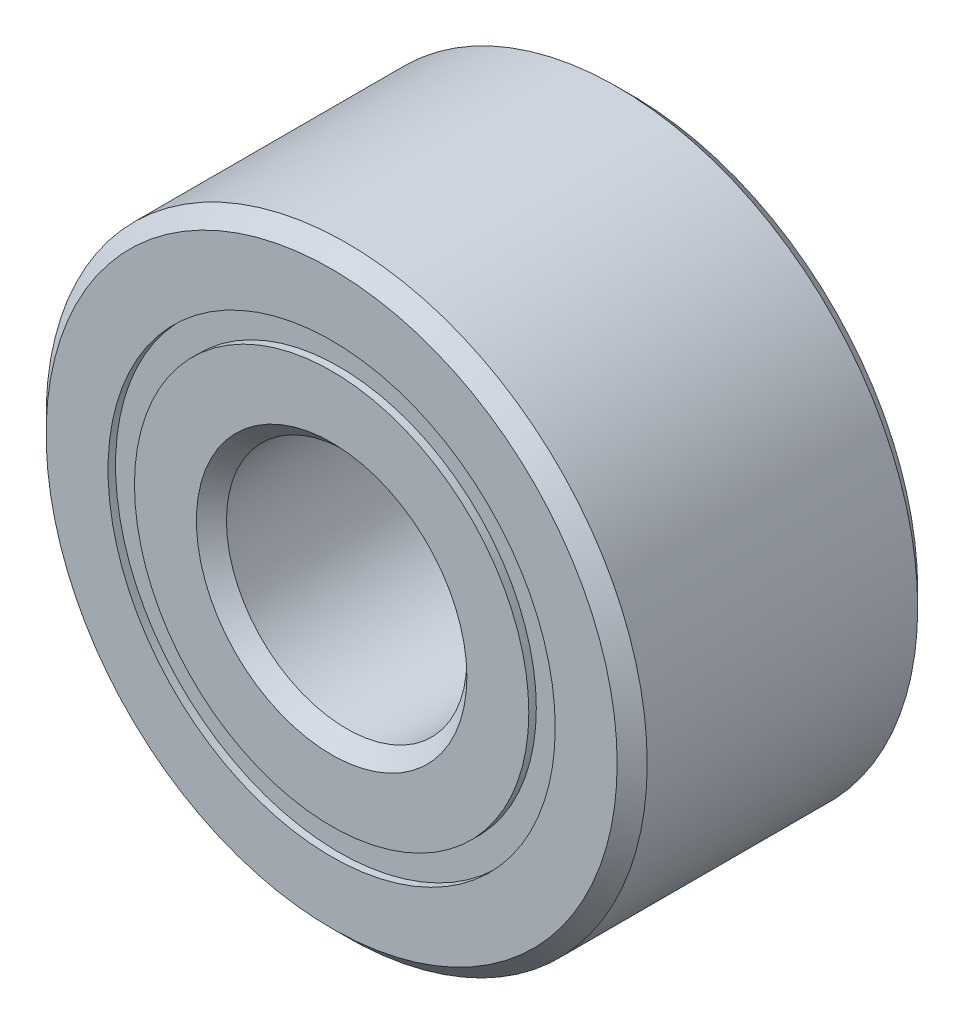
SolidWorks part; units mm, degrees
material "Stainless Steel (ferritic)"
ref_plane "Front Plane" through (0, 0, 0) normal (0, 0, 1) x (1, 0, 0)
ref_plane "Top Plane" through (0, 0, 0) normal (0, 1, 0) x (1, 0, 0)
ref_plane "Right Plane" through (0, 0, 0) normal (1, 0, 0) x (0, 0, -1)
sketch "Sketch1" plane through (0, 0, 0) normal (1, 0, 0) x (0, 0, -1)
  line L0 (-1.25, 0) -> (1.25, 0) construction
  line L1 (0, 2.5) -> (0, -2.5) construction
  line L2 (1.125, 2.5) -> (-1.125, 2.5)
  line L3 (-1.125, 2.5) -> (-1.25, 2.375)
  line L4 (-1.25, 2.375) -> (-1.25, 1.8599)
  line L5 (-1.25, 1.8599) -> (-0.5556, 1.8599)
  line L6 (1.25, 1.8599) -> (0.5556, 1.8599)
  line L7 (1.25, 2.375) -> (1.25, 1.8599)
  line L8 (1.125, 2.5) -> (1.25, 2.375)
  line L9 (0, 2.5) -> (0, 1.75) construction
  line L10 (0, 1.75) -> (0, 1) construction
  arc A0 (-0.5556, 1.8599) -> (0.5556, 1.8599) centre (0, 1.75) cw
  point P14 (0, 1)
  dimension "Width" = 2.5
  dimension "OD" = 5
  dimension "D1" = 45
  dimension "D2" = 0.125
  dimension "Shaft Dia" = 2
  dimension "D3" = 1.1111
  dimension "D4" = 0.1099
revolve "Revolve1" add sketch "Sketch1" angle 360 about L0
sketch "Sketch3" plane through (0, 0, 0) normal (1, 0, 0) x (0, 0, -1)
  line L0 (-1.25, 1.6401) -> (-0.5556, 1.6401)
  line L1 (0, 2.5) -> (0, -2.5) construction
  line L2 (-1.25, 2.375) -> (-1.25, 1.8599) construction
  line L3 (-1.25, 1.6401) -> (-1.25, 1.125)
  line L4 (-1.125, 2.5) -> (-1.25, 2.375) construction
  line L5 (-1.25, 1.125) -> (-1.125, 1)
  line L6 (-1.125, 1) -> (1.125, 1)
  line L7 (1.125, 2.5) -> (1.125, -2.5) construction
  line L8 (1.125, 1) -> (1.25, 1.125)
  line L9 (1.25, -2.375) -> (1.25, 2.375) construction
  line L10 (1.25, 1.125) -> (1.25, 1.6401)
  line L11 (1.25, 1.6401) -> (0.5556, 1.6401)
  line L13 (1.125, 2.5) -> (1.25, 2.375) construction
  arc A0 (0.5556, 1.8599) -> (-0.5556, 1.8599) centre (0, 1.75) ccw construction
  arc A1 (0.5556, 1.6401) -> (-0.5556, 1.6401) centre (0, 1.75) cw
revolve "Revolve3" add sketch "Sketch3" angle 360 about L0
sketch "Sketch4" plane through (0, 0, 0) normal (1, 0, 0) x (0, 0, -1)
  line L0 (-0.5663, 1.75) -> (0.5663, 1.75)
  arc A2 (-0.5663, 1.75) -> (0.5663, 1.75) centre (0, 1.75) cw
  arc A3 (0.5556, 1.8599) -> (-0.5556, 1.8599) centre (0, 1.75) ccw construction
revolve "Revolve4" add sketch "Sketch4" angle 360 about L0
ref_axis "Axis1" through (0, 0, -1.25) along (0, 0, 1)
pattern_circular "CirPattern1" count 8 over 360 about axis through (0, 0, -1.25) along (0, 0, 1) of bodies 104
sketch "Sketch5" plane through (0, 0, 0) normal (1, 0, 0) x (0, 0, -1)
  line L0 (-1.25, 1.8599) -> (-0.5556, 1.8599) construction
  line L1 (-1.1875, 1.8599) -> (-0.5663, 1.8599)
  line L2 (-1.1875, 1.8599) -> (-1.1875, 1.6401)
  line L3 (-1.1875, 1.6401) -> (-0.5663, 1.6401)
  line L4 (-0.5663, 1.8599) -> (-0.5663, 1.6401)
  line L5 (-1.25, 1.6401) -> (-0.5556, 1.6401) construction
  line L6 (1.25, 1.8599) -> (0.5556, 1.8599) construction
  line L7 (1.1875, 1.8599) -> (0.5663, 1.8599)
  line L8 (1.1875, 1.8599) -> (1.1875, 1.6401)
  line L9 (1.1875, 1.6401) -> (0.5663, 1.6401)
  line L10 (0.5663, 1.8599) -> (0.5663, 1.6401)
  line L11 (1.25, 1.6401) -> (0.5556, 1.6401) construction
  line L12 (-1.125, 2.5) -> (-1.25, 2.375) construction
  point P18 (-1.1875, 2.4375)
revolve "Revolve5" add sketch "Sketch5" angle 360 about L0
sketch "Sketch6" plane through (0, 0, 0) normal (1, 0, 0) x (0, 0, -1)
  line L0 (1.25, 0) -> (-1.25, 0) construction
  line L1 (1.25, 1.8599) -> (0.15, 1.8599)
  line L2 (1.25, 1.8599) -> (1.25, 9.5)
  line L3 (1.25, 9.5) -> (0.15, 9.5)
  line L4 (0.15, 1.8599) -> (0.15, 9.5)
  dimension "Th" = 1.1
  dimension "Flange OD" = 19
revolve "Revolve6" [suppressed] add sketch "Sketch6" angle 360 about L0
equation "\"D2@Sketch1\" = \"Width@Sketch1\"*.05"
equation "\"D3@Sketch1\" = \"Width@Sketch1\"/2.25"
equation "\"D4@Sketch1\" = (((\"OD@Sketch1\"-\"Width@Sketch1\")/2)/3.25)/3.5"
